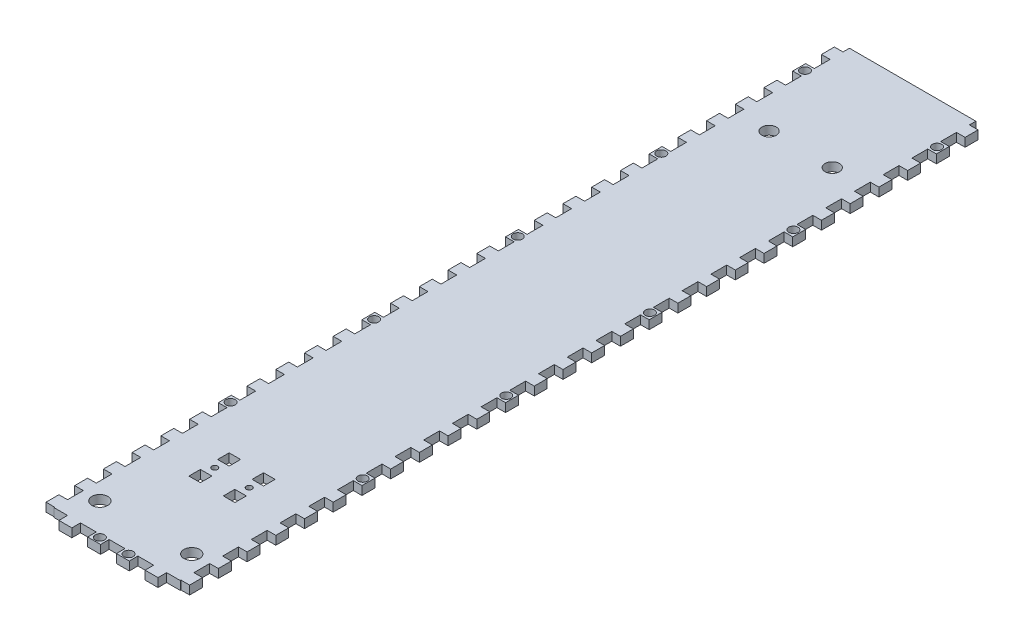
SolidWorks part; units mm, degrees
ref_plane "Plan de face" through (0, 0, 0) normal (0, 0, 1) x (1, 0, 0)
ref_plane "Plan de dessus" through (0, 0, 0) normal (0, 1, 0) x (1, 0, 0)
ref_plane "Plan de droite" through (0, 0, 0) normal (1, 0, 0) x (0, 0, -1)
sketch "Sketch1" plane through (0, 0, 0) normal (0, 0, 1) x (1, 0, 0)
  line L1 (-30.0201, 10.5217) -> (13.9799, 10.5217)
  line L2 (-30.0201, 10.5217) -> (-30.0201, 7.5217)
  line L3 (-30.0201, 7.5217) -> (13.9799, 7.5217)
  line L4 (13.9799, 10.5217) -> (13.9799, 7.5217)
  dimension "D1" = 44
  dimension "D2" = 3
extrude "Boss-Extrude1" add sketch "Sketch1" along normal blind 277
sketch "Sketch4" plane through (13.9799, 0, 0) normal (1, 0, 0) x (0, 0, -1)
  line L0 (-277, 10.5217) -> (0, 10.5217) construction
  line L1 (-276.75, 10.5217) -> (-272.25, 10.5217)
  line L2 (-276.75, 10.5217) -> (-276.75, 7.5217)
  line L3 (-276.75, 7.5217) -> (-272.25, 7.5217)
  line L4 (-272.25, 10.5217) -> (-272.25, 7.5217)
  line L5 (-277, 7.5217) -> (0, 7.5217) construction
  line L6 (-277, 7.5217) -> (-277, 10.5217) construction
  line L7 (-266.75, 10.5217) -> (-266.75, 7.5217)
  line L8 (-266.75, 10.5217) -> (-262.25, 10.5217)
  line L9 (-262.25, 10.5217) -> (-262.25, 7.5217)
  line L10 (-266.75, 7.5217) -> (-262.25, 7.5217)
  line L11 (-256.75, 10.5217) -> (-256.75, 7.5217)
  line L12 (-256.75, 10.5217) -> (-252.25, 10.5217)
  line L13 (-252.25, 10.5217) -> (-252.25, 7.5217)
  line L14 (-256.75, 7.5217) -> (-252.25, 7.5217)
  line L15 (-246.75, 10.5217) -> (-246.75, 7.5217)
  line L16 (-246.75, 10.5217) -> (-242.25, 10.5217)
  line L17 (-242.25, 10.5217) -> (-242.25, 7.5217)
  line L18 (-246.75, 7.5217) -> (-242.25, 7.5217)
  line L19 (-236.75, 10.5217) -> (-236.75, 7.5217)
  line L20 (-236.75, 10.5217) -> (-232.25, 10.5217)
  line L21 (-232.25, 10.5217) -> (-232.25, 7.5217)
  line L22 (-236.75, 7.5217) -> (-232.25, 7.5217)
  line L23 (-226.75, 10.5217) -> (-226.75, 7.5217)
  line L24 (-226.75, 10.5217) -> (-222.25, 10.5217)
  line L25 (-222.25, 10.5217) -> (-222.25, 7.5217)
  line L26 (-226.75, 7.5217) -> (-222.25, 7.5217)
  line L27 (-216.75, 10.5217) -> (-216.75, 7.5217)
  line L28 (-216.75, 10.5217) -> (-212.25, 10.5217)
  line L29 (-212.25, 10.5217) -> (-212.25, 7.5217)
  line L30 (-216.75, 7.5217) -> (-212.25, 7.5217)
  line L31 (-206.75, 10.5217) -> (-206.75, 7.5217)
  line L32 (-206.75, 10.5217) -> (-202.25, 10.5217)
  line L33 (-202.25, 10.5217) -> (-202.25, 7.5217)
  line L34 (-206.75, 7.5217) -> (-202.25, 7.5217)
  line L35 (-196.75, 10.5217) -> (-196.75, 7.5217)
  line L36 (-196.75, 10.5217) -> (-192.25, 10.5217)
  line L37 (-192.25, 10.5217) -> (-192.25, 7.5217)
  line L38 (-196.75, 7.5217) -> (-192.25, 7.5217)
  line L39 (-186.75, 10.5217) -> (-186.75, 7.5217)
  line L40 (-186.75, 10.5217) -> (-182.25, 10.5217)
  line L41 (-182.25, 10.5217) -> (-182.25, 7.5217)
  line L42 (-186.75, 7.5217) -> (-182.25, 7.5217)
  line L43 (-176.75, 10.5217) -> (-176.75, 7.5217)
  line L44 (-176.75, 10.5217) -> (-172.25, 10.5217)
  line L45 (-172.25, 10.5217) -> (-172.25, 7.5217)
  line L46 (-176.75, 7.5217) -> (-172.25, 7.5217)
  line L47 (-166.75, 10.5217) -> (-166.75, 7.5217)
  line L48 (-166.75, 10.5217) -> (-162.25, 10.5217)
  line L49 (-162.25, 10.5217) -> (-162.25, 7.5217)
  line L50 (-166.75, 7.5217) -> (-162.25, 7.5217)
  line L51 (-156.75, 10.5217) -> (-156.75, 7.5217)
  line L52 (-156.75, 10.5217) -> (-152.25, 10.5217)
  line L53 (-152.25, 10.5217) -> (-152.25, 7.5217)
  line L54 (-156.75, 7.5217) -> (-152.25, 7.5217)
  line L55 (-146.75, 10.5217) -> (-146.75, 7.5217)
  line L56 (-146.75, 10.5217) -> (-142.25, 10.5217)
  line L57 (-142.25, 10.5217) -> (-142.25, 7.5217)
  line L58 (-146.75, 7.5217) -> (-142.25, 7.5217)
  line L59 (-136.75, 10.5217) -> (-136.75, 7.5217)
  line L60 (-136.75, 10.5217) -> (-132.25, 10.5217)
  line L61 (-132.25, 10.5217) -> (-132.25, 7.5217)
  line L62 (-136.75, 7.5217) -> (-132.25, 7.5217)
  line L63 (-126.75, 10.5217) -> (-126.75, 7.5217)
  line L64 (-126.75, 10.5217) -> (-122.25, 10.5217)
  line L65 (-122.25, 10.5217) -> (-122.25, 7.5217)
  line L66 (-126.75, 7.5217) -> (-122.25, 7.5217)
  line L67 (-116.75, 10.5217) -> (-116.75, 7.5217)
  line L68 (-116.75, 10.5217) -> (-112.25, 10.5217)
  line L69 (-112.25, 10.5217) -> (-112.25, 7.5217)
  line L70 (-116.75, 7.5217) -> (-112.25, 7.5217)
  line L71 (-106.75, 10.5217) -> (-106.75, 7.5217)
  line L72 (-106.75, 10.5217) -> (-102.25, 10.5217)
  line L73 (-102.25, 10.5217) -> (-102.25, 7.5217)
  line L74 (-106.75, 7.5217) -> (-102.25, 7.5217)
  line L75 (-96.75, 10.5217) -> (-96.75, 7.5217)
  line L76 (-96.75, 10.5217) -> (-92.25, 10.5217)
  line L77 (-92.25, 10.5217) -> (-92.25, 7.5217)
  line L78 (-96.75, 7.5217) -> (-92.25, 7.5217)
  line L79 (-86.75, 10.5217) -> (-86.75, 7.5217)
  line L80 (-86.75, 10.5217) -> (-82.25, 10.5217)
  line L81 (-82.25, 10.5217) -> (-82.25, 7.5217)
  line L82 (-86.75, 7.5217) -> (-82.25, 7.5217)
  line L83 (-76.75, 10.5217) -> (-76.75, 7.5217)
  line L84 (-76.75, 10.5217) -> (-72.25, 10.5217)
  line L85 (-72.25, 10.5217) -> (-72.25, 7.5217)
  line L86 (-76.75, 7.5217) -> (-72.25, 7.5217)
  line L87 (-66.75, 10.5217) -> (-66.75, 7.5217)
  line L88 (-66.75, 10.5217) -> (-62.25, 10.5217)
  line L89 (-62.25, 10.5217) -> (-62.25, 7.5217)
  line L90 (-66.75, 7.5217) -> (-62.25, 7.5217)
  line L91 (-56.75, 10.5217) -> (-56.75, 7.5217)
  line L92 (-56.75, 10.5217) -> (-52.25, 10.5217)
  line L93 (-52.25, 10.5217) -> (-52.25, 7.5217)
  line L94 (-56.75, 7.5217) -> (-52.25, 7.5217)
  line L95 (-46.75, 10.5217) -> (-46.75, 7.5217)
  line L96 (-46.75, 10.5217) -> (-42.25, 10.5217)
  line L97 (-42.25, 10.5217) -> (-42.25, 7.5217)
  line L98 (-46.75, 7.5217) -> (-42.25, 7.5217)
  line L99 (-36.75, 10.5217) -> (-36.75, 7.5217)
  line L100 (-36.75, 10.5217) -> (-32.25, 10.5217)
  line L101 (-32.25, 10.5217) -> (-32.25, 7.5217)
  line L102 (-36.75, 7.5217) -> (-32.25, 7.5217)
  line L103 (-26.75, 10.5217) -> (-26.75, 7.5217)
  line L104 (-26.75, 10.5217) -> (-22.25, 10.5217)
  line L105 (-22.25, 10.5217) -> (-22.25, 7.5217)
  line L106 (-26.75, 7.5217) -> (-22.25, 7.5217)
  line L107 (-16.75, 10.5217) -> (-16.75, 7.5217)
  line L108 (-16.75, 10.5217) -> (-12.25, 10.5217)
  line L109 (-12.25, 10.5217) -> (-12.25, 7.5217)
  line L110 (-16.75, 7.5217) -> (-12.25, 7.5217)
  line L111 (-6.75, 10.5217) -> (-6.75, 7.5217)
  line L112 (-6.75, 10.5217) -> (-2.25, 10.5217)
  line L113 (-2.25, 10.5217) -> (-2.25, 7.5217)
  line L114 (-6.75, 7.5217) -> (-2.25, 7.5217)
  dimension "D1" = 0.25
  dimension "D2" = 4.5
  dimension "D3" = 28
extrude "Boss-Extrude2" add sketch "Sketch4" along normal blind 3
sketch "Sketch5" plane through (-30.0201, 0, 0) normal (-1, 0, 0) x (0, 0, 1)
  line L0 (277, 7.5217) -> (0, 7.5217) construction
  line L1 (276.75, 7.5217) -> (272.25, 7.5217)
  line L2 (276.75, 7.5217) -> (276.75, 10.5217)
  line L3 (276.75, 10.5217) -> (272.25, 10.5217)
  line L4 (272.25, 7.5217) -> (272.25, 10.5217)
  line L5 (277, 10.5217) -> (0, 10.5217) construction
  line L6 (277, 10.5217) -> (277, 7.5217) construction
  line L7 (266.75, 7.5217) -> (266.75, 10.5217)
  line L8 (266.75, 7.5217) -> (262.25, 7.5217)
  line L9 (262.25, 7.5217) -> (262.25, 10.5217)
  line L10 (266.75, 10.5217) -> (262.25, 10.5217)
  line L11 (256.75, 7.5217) -> (256.75, 10.5217)
  line L12 (256.75, 7.5217) -> (252.25, 7.5217)
  line L13 (252.25, 7.5217) -> (252.25, 10.5217)
  line L14 (256.75, 10.5217) -> (252.25, 10.5217)
  line L15 (246.75, 7.5217) -> (246.75, 10.5217)
  line L16 (246.75, 7.5217) -> (242.25, 7.5217)
  line L17 (242.25, 7.5217) -> (242.25, 10.5217)
  line L18 (246.75, 10.5217) -> (242.25, 10.5217)
  line L19 (236.75, 7.5217) -> (236.75, 10.5217)
  line L20 (236.75, 7.5217) -> (232.25, 7.5217)
  line L21 (232.25, 7.5217) -> (232.25, 10.5217)
  line L22 (236.75, 10.5217) -> (232.25, 10.5217)
  line L23 (226.75, 7.5217) -> (226.75, 10.5217)
  line L24 (226.75, 7.5217) -> (222.25, 7.5217)
  line L25 (222.25, 7.5217) -> (222.25, 10.5217)
  line L26 (226.75, 10.5217) -> (222.25, 10.5217)
  line L27 (216.75, 7.5217) -> (216.75, 10.5217)
  line L28 (216.75, 7.5217) -> (212.25, 7.5217)
  line L29 (212.25, 7.5217) -> (212.25, 10.5217)
  line L30 (216.75, 10.5217) -> (212.25, 10.5217)
  line L31 (206.75, 7.5217) -> (206.75, 10.5217)
  line L32 (206.75, 7.5217) -> (202.25, 7.5217)
  line L33 (202.25, 7.5217) -> (202.25, 10.5217)
  line L34 (206.75, 10.5217) -> (202.25, 10.5217)
  line L35 (196.75, 7.5217) -> (196.75, 10.5217)
  line L36 (196.75, 7.5217) -> (192.25, 7.5217)
  line L37 (192.25, 7.5217) -> (192.25, 10.5217)
  line L38 (196.75, 10.5217) -> (192.25, 10.5217)
  line L39 (186.75, 7.5217) -> (186.75, 10.5217)
  line L40 (186.75, 7.5217) -> (182.25, 7.5217)
  line L41 (182.25, 7.5217) -> (182.25, 10.5217)
  line L42 (186.75, 10.5217) -> (182.25, 10.5217)
  line L43 (176.75, 7.5217) -> (176.75, 10.5217)
  line L44 (176.75, 7.5217) -> (172.25, 7.5217)
  line L45 (172.25, 7.5217) -> (172.25, 10.5217)
  line L46 (176.75, 10.5217) -> (172.25, 10.5217)
  line L47 (166.75, 7.5217) -> (166.75, 10.5217)
  line L48 (166.75, 7.5217) -> (162.25, 7.5217)
  line L49 (162.25, 7.5217) -> (162.25, 10.5217)
  line L50 (166.75, 10.5217) -> (162.25, 10.5217)
  line L51 (156.75, 7.5217) -> (156.75, 10.5217)
  line L52 (156.75, 7.5217) -> (152.25, 7.5217)
  line L53 (152.25, 7.5217) -> (152.25, 10.5217)
  line L54 (156.75, 10.5217) -> (152.25, 10.5217)
  line L55 (146.75, 7.5217) -> (146.75, 10.5217)
  line L56 (146.75, 7.5217) -> (142.25, 7.5217)
  line L57 (142.25, 7.5217) -> (142.25, 10.5217)
  line L58 (146.75, 10.5217) -> (142.25, 10.5217)
  line L59 (136.75, 7.5217) -> (136.75, 10.5217)
  line L60 (136.75, 7.5217) -> (132.25, 7.5217)
  line L61 (132.25, 7.5217) -> (132.25, 10.5217)
  line L62 (136.75, 10.5217) -> (132.25, 10.5217)
  line L63 (126.75, 7.5217) -> (126.75, 10.5217)
  line L64 (126.75, 7.5217) -> (122.25, 7.5217)
  line L65 (122.25, 7.5217) -> (122.25, 10.5217)
  line L66 (126.75, 10.5217) -> (122.25, 10.5217)
  line L67 (116.75, 7.5217) -> (116.75, 10.5217)
  line L68 (116.75, 7.5217) -> (112.25, 7.5217)
  line L69 (112.25, 7.5217) -> (112.25, 10.5217)
  line L70 (116.75, 10.5217) -> (112.25, 10.5217)
  line L71 (106.75, 7.5217) -> (106.75, 10.5217)
  line L72 (106.75, 7.5217) -> (102.25, 7.5217)
  line L73 (102.25, 7.5217) -> (102.25, 10.5217)
  line L74 (106.75, 10.5217) -> (102.25, 10.5217)
  line L75 (96.75, 7.5217) -> (96.75, 10.5217)
  line L76 (96.75, 7.5217) -> (92.25, 7.5217)
  line L77 (92.25, 7.5217) -> (92.25, 10.5217)
  line L78 (96.75, 10.5217) -> (92.25, 10.5217)
  line L79 (86.75, 7.5217) -> (86.75, 10.5217)
  line L80 (86.75, 7.5217) -> (82.25, 7.5217)
  line L81 (82.25, 7.5217) -> (82.25, 10.5217)
  line L82 (86.75, 10.5217) -> (82.25, 10.5217)
  line L83 (76.75, 7.5217) -> (76.75, 10.5217)
  line L84 (76.75, 7.5217) -> (72.25, 7.5217)
  line L85 (72.25, 7.5217) -> (72.25, 10.5217)
  line L86 (76.75, 10.5217) -> (72.25, 10.5217)
  line L87 (66.75, 7.5217) -> (66.75, 10.5217)
  line L88 (66.75, 7.5217) -> (62.25, 7.5217)
  line L89 (62.25, 7.5217) -> (62.25, 10.5217)
  line L90 (66.75, 10.5217) -> (62.25, 10.5217)
  line L91 (56.75, 7.5217) -> (56.75, 10.5217)
  line L92 (56.75, 7.5217) -> (52.25, 7.5217)
  line L93 (52.25, 7.5217) -> (52.25, 10.5217)
  line L94 (56.75, 10.5217) -> (52.25, 10.5217)
  line L95 (46.75, 7.5217) -> (46.75, 10.5217)
  line L96 (46.75, 7.5217) -> (42.25, 7.5217)
  line L97 (42.25, 7.5217) -> (42.25, 10.5217)
  line L98 (46.75, 10.5217) -> (42.25, 10.5217)
  line L99 (36.75, 7.5217) -> (36.75, 10.5217)
  line L100 (36.75, 7.5217) -> (32.25, 7.5217)
  line L101 (32.25, 7.5217) -> (32.25, 10.5217)
  line L102 (36.75, 10.5217) -> (32.25, 10.5217)
  line L103 (26.75, 7.5217) -> (26.75, 10.5217)
  line L104 (26.75, 7.5217) -> (22.25, 7.5217)
  line L105 (22.25, 7.5217) -> (22.25, 10.5217)
  line L106 (26.75, 10.5217) -> (22.25, 10.5217)
  line L107 (16.75, 7.5217) -> (16.75, 10.5217)
  line L108 (16.75, 7.5217) -> (12.25, 7.5217)
  line L109 (12.25, 7.5217) -> (12.25, 10.5217)
  line L110 (16.75, 10.5217) -> (12.25, 10.5217)
  line L111 (6.75, 7.5217) -> (6.75, 10.5217)
  line L112 (6.75, 7.5217) -> (2.25, 7.5217)
  line L113 (2.25, 7.5217) -> (2.25, 10.5217)
  line L114 (6.75, 10.5217) -> (2.25, 10.5217)
  dimension "D1" = 0.25
  dimension "D2" = 4.5
  dimension "D3" = 28
extrude "Boss-Extrude3" add sketch "Sketch5" along normal blind 3
sketch "Sketch6" plane through (0, 0, 277) normal (0, 0, 1) x (1, 0, 0)
  line L0 (13.9799, 10.5217) -> (-30.0201, 10.5217) construction
  line L1 (-25.2701, 10.5217) -> (-20.7701, 10.5217)
  line L2 (-25.2701, 10.5217) -> (-25.2701, 7.5217)
  line L3 (-25.2701, 7.5217) -> (-20.7701, 7.5217)
  line L4 (-20.7701, 10.5217) -> (-20.7701, 7.5217)
  line L5 (-30.0201, 7.5217) -> (13.9799, 7.5217) construction
  line L6 (-30.0201, 7.5217) -> (-30.0201, 10.5217) construction
  line L7 (-15.2701, 10.5217) -> (-15.2701, 7.5217)
  line L8 (-15.2701, 10.5217) -> (-10.7701, 10.5217)
  line L9 (-10.7701, 10.5217) -> (-10.7701, 7.5217)
  line L10 (-15.2701, 7.5217) -> (-10.7701, 7.5217)
  line L11 (-5.2701, 10.5217) -> (-5.2701, 7.5217)
  line L12 (-5.2701, 10.5217) -> (-0.7701, 10.5217)
  line L13 (-0.7701, 10.5217) -> (-0.7701, 7.5217)
  line L14 (-5.2701, 7.5217) -> (-0.7701, 7.5217)
  line L15 (4.7299, 10.5217) -> (4.7299, 7.5217)
  line L16 (4.7299, 10.5217) -> (9.2299, 10.5217)
  line L17 (9.2299, 10.5217) -> (9.2299, 7.5217)
  line L18 (4.7299, 7.5217) -> (9.2299, 7.5217)
  dimension "D1" = 4.75
  dimension "D2" = 4.5
  dimension "D3" = 4
extrude "Boss-Extrude4" add sketch "Sketch6" along normal blind 3
sketch "Sketch7" plane through (0, 7.5217, 0) normal (0, -1, 0) x (1, 0, 0)
  line L0 (-8.0201, 277) -> (-8.0201, 0) construction
  line L1 (-10.7701, 277) -> (-5.2701, 277) construction
  line L2 (-30.0201, 0) -> (13.9799, 0) construction
  line L3 (13.9799, 276.75) -> (16.9799, 272.25) construction
  line L4 (16.9799, 266.75) -> (16.9799, 262.25) construction
  line L5 (16.9799, 276.75) -> (13.9799, 276.75) construction
  circle A0 centre (14.9799, 264.5) radius 1.6
  circle A1 centre (-31.0201, 264.5) radius 1.6
  circle A2 centre (-31.0201, 214.5) radius 1.6
  circle A3 centre (14.9799, 214.5) radius 1.6
  circle A4 centre (-31.0201, 164.5) radius 1.6
  circle A5 centre (14.9799, 164.5) radius 1.6
  circle A6 centre (-31.0201, 114.5) radius 1.6
  circle A7 centre (14.9799, 114.5) radius 1.6
  circle A8 centre (-31.0201, 64.5) radius 1.6
  circle A9 centre (14.9799, 64.5) radius 1.6
  circle A10 centre (-31.0201, 14.5) radius 1.6
  circle A11 centre (14.9799, 14.5) radius 1.6
  dimension "D1" = 6
  dimension "D3" = 3.2
  dimension "D4" = 2
  dimension "D2" = 12.25
extrude "Cut-Extrude1" cut sketch "Sketch7" against normal blind 3
sketch "Sketch8" plane through (0, 7.5217, 0) normal (0, -1, 0) x (1, 0, 0)
  line L0 (-8.0201, 0) -> (-8.0201, 54.5316) construction
  line L1 (-30.0201, 0) -> (13.9799, 0) construction
  circle A0 centre (-19.0201, 39) radius 2.5
  circle A1 centre (2.9799, 39) radius 2.5
  dimension "D1" = 5
  dimension "D2" = 11
  dimension "D3" = 39
extrude "Cut-Extrude2" cut sketch "Sketch8" against normal blind 12
sketch "Sketch9" plane through (0, 7.5217, 0) normal (0, -1, 0) x (-1, 0, 0)
  line L0 (15.2701, -280) -> (10.7701, -280) construction
  line L1 (5.2701, -280) -> (0.7701, -280) construction
  circle A0 centre (13.0201, -278) radius 1.6
  circle A1 centre (3.0201, -278) radius 1.6
  dimension "D1" = 3.2
  dimension "D2" = 3.2
  dimension "D3" = 2
  dimension "D4" = 2
extrude "Cut-Extrude3" cut sketch "Sketch9" against normal blind 12
sketch "Sketch11" plane through (0, 7.5217, 0) normal (0, -1, 0) x (1, 0, 0)
  line L0 (-10.7701, 277) -> (-5.2701, 277) construction
  line L1 (-16.0201, 244) -> (-12.0201, 244)
  line L2 (-16.0201, 244) -> (-16.0201, 240)
  line L3 (-16.0201, 240) -> (-12.0201, 240)
  line L4 (-12.0201, 244) -> (-12.0201, 240)
  line L5 (-16.0201, 234) -> (-12.0201, 234)
  line L6 (-16.0201, 234) -> (-16.0201, 230)
  line L7 (-16.0201, 230) -> (-12.0201, 230)
  line L8 (-12.0201, 234) -> (-12.0201, 230)
  line L9 (-4.0201, 244) -> (-0.0201, 244)
  line L10 (-4.0201, 244) -> (-4.0201, 240)
  line L11 (-4.0201, 240) -> (-0.0201, 240)
  line L12 (-0.0201, 244) -> (-0.0201, 240)
  line L13 (-4.0201, 234) -> (-0.0201, 234)
  line L14 (-4.0201, 234) -> (-4.0201, 230)
  line L15 (-4.0201, 230) -> (-0.0201, 230)
  line L16 (-0.0201, 234) -> (-0.0201, 230)
  circle A0 centre (-14.0201, 237) radius 1
  circle A1 centre (-2.0201, 237) radius 1
  point P11 (-8.0201, 277)
  point P23 (-14.0201, 240)
  point P26 (-2.0201, 240)
  dimension "D14" = 2
  dimension "D15" = 2
  dimension "D1" = 4
  dimension "D2" = 4
  dimension "D3" = 4
  dimension "D4" = 4
  dimension "D5" = 4
  dimension "D6" = 6
  dimension "D7" = 4
  dimension "D8" = 4
  dimension "D9" = 4
  dimension "D10" = 4
  dimension "D11" = 6
  dimension "D12" = 8
  dimension "D13" = 33
  dimension "D16" = 3
extrude "Cut-Extrude4" cut sketch "Sketch11" against normal blind 10
sketch "Sketch12" plane through (0, 7.5217, 0) normal (0, -1, 0) x (1, 0, 0)
  line L2 (-10.7701, 277) -> (-5.2701, 277) construction
  circle A0 centre (-24.0201, 267) radius 2.75
  circle A1 centre (7.9799, 267) radius 2.75
  point P6 (-8.0201, 277)
  dimension "D1" = 5.5
  dimension "D2" = 5.5
  dimension "D3" = 32
  dimension "D4" = 16
  dimension "D5" = 10
extrude "Cut-Extrude5" cut sketch "Sketch12" against normal blind 10
extrude "Boss-Extrude5" add sketch "Sketch7<2>" against normal through all contours A1 | A0 region at (14.9799, 7.5217, 264.5) region at (-31.0201, 7.5217, 264.5)
sketch "Sketch7<2>" plane through (0, 7.5217, 0) normal (0, -1, 0) x (1, 0, 0) same geometry as "Sketch7"
